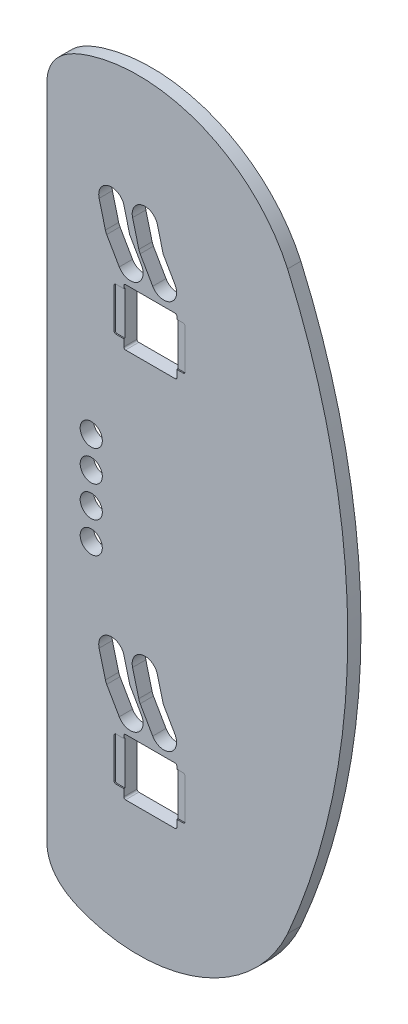
SolidWorks part; units mm, degrees
material "Pine"
ref_plane "Front Plane" through (0, 0, 0) normal (0, 0, 1) x (1, 0, 0)
ref_plane "Top Plane" through (0, 0, 0) normal (0, 1, 0) x (1, 0, 0)
ref_plane "Right Plane" through (0, 0, 0) normal (1, 0, 0) x (0, 0, -1)
sketch "Sketch1" plane through (0, 0, 0) normal (0, 1, 0) x (1, 0, 0)
  line L0 (-92.9216, 89.0184) -> (669.0784, 89.0184)
  line L1 (669.0784, 89.0184) -> (669.0784, 419.2184)
  line L2 (-92.9216, 89.0184) -> (-92.9216, 419.2184)
  line L5 (110.2784, 495.4184) -> (465.8784, 495.4184)
  line L8 (110.2784, 495.4184) -> (-92.9216, 419.2184)
  line L9 (465.8784, 495.4184) -> (669.0784, 419.2184)
  line L10 (-92.9216, 495.4184) -> (669.0784, 495.4184) construction
sketch "Sketch2" plane through (0, 0, 0) normal (0, 0, 1) x (1, 0, 0)
  line L95 (1361.0966, 1819.7347) -> (1361.0966, 996.3635)
  arc A0 (1691.2966, 1027.0491) -> (1691.2966, 1789.0491) centre (733.0004, 1408.0491) ccw
  spline S0 degree 3 poles (1691.2966, 1027.0491) (1656.7077, 922.0591) (1371.3251, 886.2968) (1361.0966, 996.3635) knots 0 0 0 0 7.629784 7.629784 7.629784 7.629784
  spline S1 degree 3 poles (1691.2966, 1789.0491) (1656.7629, 1894.0573) (1371.3251, 1929.8013) (1361.0966, 1819.7347) knots 0 0 0 0 7.638295 7.638295 7.638295 7.638295
sketch "Sketch5" plane through (0, 0, 0) normal (0, 0, 1) x (1, 0, 0)
  line L0 (1361.0966, 1819.7347) -> (1361.0966, 996.3635)
  line L1 (1361.0966, 1789.0491) -> (1361.0966, 1027.0491)
  line L2 (1540.0357, 1006.8697) -> (1540.0357, 1016.3947)
  line L3 (1486.0607, 1097.3572) -> (1486.0607, 1006.8697) construction
  line L4 (1486.0607, 1102.1197) -> (1486.0607, 1092.5947)
  line L5 (1540.0357, 1006.8697) -> (1540.0357, 1097.3572) construction
  line L6 (1544.7982, 1102.1197) -> (1481.2982, 1102.1197) construction
  line L7 (1486.0607, 1006.8697) -> (1540.0357, 1006.8697)
  line L8 (1479.7107, 1016.3947) -> (1546.3857, 1016.3947)
  line L9 (1546.3857, 1016.3947) -> (1546.3857, 1092.5947)
  line L10 (1546.3857, 1092.5947) -> (1479.7107, 1092.5947)
  line L11 (1479.7107, 1016.3947) -> (1479.7107, 1092.5947)
  line L12 (1540.0357, 1548.8399) -> (1540.0357, 1558.3649)
  line L13 (1486.0607, 1548.8399) -> (1540.0357, 1548.8399)
  line L14 (1546.3857, 1634.5649) -> (1479.7107, 1634.5649)
  line L15 (1486.0607, 1644.0899) -> (1486.0607, 1634.5649)
  line L16 (1479.7107, 1558.3649) -> (1479.7107, 1634.5649)
  line L17 (1540.0357, 1644.0899) -> (1486.0607, 1644.0899)
  line L18 (1479.7107, 1558.3649) -> (1546.3857, 1558.3649)
  line L19 (1546.3857, 1558.3649) -> (1546.3857, 1634.5649)
  line L20 (1540.0357, 1092.5947) -> (1540.0357, 1102.1197)
  line L21 (1486.0607, 1016.3947) -> (1486.0607, 1006.8697)
  line L22 (1540.0357, 1634.5649) -> (1540.0357, 1644.0899)
  line L23 (1486.0607, 1558.3649) -> (1486.0607, 1548.8399)
  line L95 (1361.0966, 1819.7347) -> (1361.0966, 996.3635)
  line L115 (1540.0357, 1102.1197) -> (1486.0607, 1102.1197)
  line L199 (1363.2449, 1823.8418) -> (1361.0966, 1819.7347)
  line L200 (1361.0966, 1819.7347) -> (1361.7967, 1824.3165)
  line L201 (1361.7967, 1824.3165) -> (1363.2449, 1823.8418)
  line L202 (1540.0357, 1097.3572) -> (1486.0607, 1097.3572) construction
  line L203 (1481.2982, 1102.1197) -> (1481.2982, 1006.8697) construction
  line L204 (1544.7982, 1006.8697) -> (1544.7982, 1102.1197) construction
  arc A0 (1691.2966, 1027.0491) -> (1691.2966, 1789.0491) centre (733.0004, 1408.0491) ccw
  circle A1 centre (1506.0488, 1194.0197) radius 15.875
  circle A2 centre (1515.0488, 1159.0198) radius 15.875
  circle A3 centre (1533.0488, 1127.7698) radius 15.875
  circle A4 centre (1467.0488, 1159.0198) radius 15.875
  circle A5 centre (1485.0488, 1127.7698) radius 15.875
  circle A6 centre (1458.0488, 1194.0197) radius 15.875
  circle A7 centre (1513.0482, 1054.4947) radius 12
  circle A8 centre (1506.0488, 1735.9899) radius 15.875
  circle A9 centre (1515.0488, 1700.99) radius 15.875
  circle A10 centre (1533.0488, 1669.74) radius 15.875
  circle A11 centre (1467.0488, 1700.99) radius 15.875
  circle A12 centre (1485.0488, 1669.74) radius 15.875
  circle A13 centre (1458.0488, 1735.9899) radius 15.875
  circle A15 centre (1483.5084, 1375.1967) radius 12
  circle A16 centre (1483.9827, 1438.6917) radius 12
  circle A17 centre (1551.8392, 1408.0266) radius 29.9999
  circle A18 centre (1409.3368, 1408.0266) radius 15.9995
  circle A19 centre (1513.0482, 1596.4649) radius 12
  arc A30 (1539.4945, 1725.9331) -> (1482.0488, 1761.3623) centre (1506.0488, 1735.9899) ccw
  arc A32 (1549.9668, 1700.2938) -> (1539.4945, 1725.9331) centre (1515.0488, 1700.99) ccw
  arc A41 (1509.0488, 1644.3676) -> (1549.9668, 1700.2938) centre (1533.0488, 1669.74) ccw
  arc A46 (1450.1308, 1670.4362) -> (1509.0488, 1644.3676) centre (1485.0488, 1669.74) ccw
  arc A47 (1433.6031, 1711.0467) -> (1450.1308, 1670.4362) centre (1467.0488, 1700.99) ccw
  arc A50 (1482.0488, 1761.3623) -> (1433.6031, 1711.0467) centre (1458.0488, 1735.9899) ccw
  arc A64 (1509.0488, 1102.3974) -> (1549.9668, 1158.3235) centre (1533.0488, 1127.7698) ccw
  arc A66 (1450.1308, 1128.466) -> (1509.0488, 1102.3974) centre (1485.0488, 1127.7698) ccw
  arc A68 (1433.6031, 1169.0765) -> (1450.1308, 1128.466) centre (1467.0488, 1159.0198) ccw
  arc A70 (1539.4945, 1183.9629) -> (1482.0488, 1219.3921) centre (1506.0488, 1194.0197) ccw
  arc A72 (1549.9668, 1158.3235) -> (1539.4945, 1183.9629) centre (1515.0488, 1159.0198) ccw
  arc A73 (1482.0488, 1219.3921) -> (1433.6031, 1169.0765) centre (1458.0488, 1194.0197) ccw
  arc A86 (1474.249, 1382.8299) -> (1489.0021, 1364.5282) centre (1483.5084, 1375.1967) ccw
  arc A89 (1488.8753, 1449.649) -> (1474.6166, 1431.19) centre (1483.9827, 1438.6917) ccw
  arc A97 (1557.861, 1378.6372) -> (1557.0728, 1437.5665) centre (1551.8392, 1408.0266) ccw
  arc A99 (1420.1657, 1419.8299) -> (1400.5179, 1421.402) centre (1409.3362, 1408.0491) ccw
  arc A100 (1402.6554, 1393.5084) -> (1419.641, 1395.8067) centre (1409.3362, 1408.0491) ccw
  spline S0 degree 3 poles (1691.2966, 1027.0491) (1656.7077, 922.0591) (1371.3251, 886.2968) (1361.0966, 996.3635) knots 0 0 0 0 7.629784 7.629784 7.629784 7.629784
  spline S1 degree 3 poles (1691.2966, 1789.0491) (1656.7629, 1894.0573) (1371.3251, 1929.8013) (1361.0966, 1819.7347) knots 0 0 0 0 7.638295 7.638295 7.638295 7.638295
  dimension "D1" = 4.7625
sketch "Sketch8" plane through (0, 0, 0) normal (0, 0, 1) x (1, 0, 0)
  line L2 (1540.0357, 1006.8697) -> (1540.0357, 1016.3947)
  line L3 (1486.0607, 1097.3572) -> (1486.0607, 1006.8697) construction
  line L4 (1486.0607, 1102.1197) -> (1486.0607, 1092.5947)
  line L5 (1540.0357, 1006.8697) -> (1540.0357, 1097.3572) construction
  line L6 (1544.7982, 1102.1197) -> (1481.2982, 1102.1197) construction
  line L7 (1486.0607, 1006.8697) -> (1540.0357, 1006.8697)
  line L8 (1479.7107, 1016.3947) -> (1546.3857, 1016.3947)
  line L9 (1546.3857, 1016.3947) -> (1546.3857, 1092.5947)
  line L10 (1546.3857, 1092.5947) -> (1479.7107, 1092.5947)
  line L11 (1479.7107, 1016.3947) -> (1479.7107, 1092.5947)
  line L12 (1540.0357, 1548.8399) -> (1540.0357, 1558.3649)
  line L13 (1486.0607, 1548.8399) -> (1540.0357, 1548.8399)
  line L14 (1546.3857, 1634.5649) -> (1479.7107, 1634.5649)
  line L15 (1486.0607, 1644.0899) -> (1486.0607, 1634.5649)
  line L16 (1479.7107, 1558.3649) -> (1479.7107, 1634.5649)
  line L17 (1540.0357, 1644.0899) -> (1486.0607, 1644.0899)
  line L18 (1479.7107, 1558.3649) -> (1546.3857, 1558.3649)
  line L19 (1546.3857, 1558.3649) -> (1546.3857, 1634.5649)
  line L20 (1540.0357, 1092.5947) -> (1540.0357, 1102.1197)
  line L21 (1486.0607, 1016.3947) -> (1486.0607, 1006.8697)
  line L22 (1540.0357, 1634.5649) -> (1540.0357, 1644.0899)
  line L23 (1486.0607, 1558.3649) -> (1486.0607, 1548.8399)
  line L95 (1361.0966, 1819.7347) -> (1361.0966, 996.3635)
  line L115 (1540.0357, 1102.1197) -> (1486.0607, 1102.1197)
  line L202 (1540.0357, 1097.3572) -> (1486.0607, 1097.3572) construction
  line L203 (1481.2982, 1102.1197) -> (1481.2982, 1006.8697) construction
  line L204 (1544.7982, 1006.8697) -> (1544.7982, 1102.1197) construction
  arc A0 (1691.2966, 1027.0491) -> (1691.2966, 1789.0491) centre (733.0004, 1408.0491) ccw
  circle A1 centre (1506.0488, 1194.0197) radius 15.875
  circle A2 centre (1515.0488, 1159.0198) radius 15.875
  circle A3 centre (1533.0488, 1127.7698) radius 15.875
  circle A4 centre (1467.0488, 1159.0198) radius 15.875
  circle A5 centre (1485.0488, 1127.7698) radius 15.875
  circle A6 centre (1458.0488, 1194.0197) radius 15.875
  circle A7 centre (1513.0482, 1054.4947) radius 12
  circle A8 centre (1506.0488, 1735.9899) radius 15.875
  circle A9 centre (1515.0488, 1700.99) radius 15.875
  circle A10 centre (1533.0488, 1669.74) radius 15.875
  circle A11 centre (1467.0488, 1700.99) radius 15.875
  circle A12 centre (1485.0488, 1669.74) radius 15.875
  circle A13 centre (1458.0488, 1735.9899) radius 15.875
  circle A15 centre (1483.5084, 1375.1967) radius 12
  circle A16 centre (1483.9827, 1438.6917) radius 12
  circle A17 centre (1551.8392, 1408.0266) radius 29.9999
  circle A18 centre (1409.3368, 1408.0266) radius 15.9995
  circle A19 centre (1513.0482, 1596.4649) radius 12
  arc A30 (1539.4945, 1725.9331) -> (1482.0488, 1761.3623) centre (1506.0488, 1735.9899) ccw
  arc A32 (1549.9668, 1700.2938) -> (1539.4945, 1725.9331) centre (1515.0488, 1700.99) ccw
  arc A41 (1509.0488, 1644.3676) -> (1549.9668, 1700.2938) centre (1533.0488, 1669.74) ccw
  arc A46 (1450.1308, 1670.4362) -> (1509.0488, 1644.3676) centre (1485.0488, 1669.74) ccw
  arc A47 (1433.6031, 1711.0467) -> (1450.1308, 1670.4362) centre (1467.0488, 1700.99) ccw
  arc A50 (1482.0488, 1761.3623) -> (1433.6031, 1711.0467) centre (1458.0488, 1735.9899) ccw
  arc A64 (1509.0488, 1102.3974) -> (1549.9668, 1158.3235) centre (1533.0488, 1127.7698) ccw
  arc A66 (1450.1308, 1128.466) -> (1509.0488, 1102.3974) centre (1485.0488, 1127.7698) ccw
  arc A68 (1433.6031, 1169.0765) -> (1450.1308, 1128.466) centre (1467.0488, 1159.0198) ccw
  arc A70 (1539.4945, 1183.9629) -> (1482.0488, 1219.3921) centre (1506.0488, 1194.0197) ccw
  arc A72 (1549.9668, 1158.3235) -> (1539.4945, 1183.9629) centre (1515.0488, 1159.0198) ccw
  arc A73 (1482.0488, 1219.3921) -> (1433.6031, 1169.0765) centre (1458.0488, 1194.0197) ccw
  arc A86 (1474.249, 1382.8299) -> (1489.0021, 1364.5282) centre (1483.5084, 1375.1967) ccw
  arc A89 (1488.8753, 1449.649) -> (1474.6166, 1431.19) centre (1483.9827, 1438.6917) ccw
  arc A97 (1557.861, 1378.6372) -> (1557.0728, 1437.5665) centre (1551.8392, 1408.0266) ccw
  arc A99 (1420.1657, 1419.8299) -> (1400.5179, 1421.402) centre (1409.3362, 1408.0491) ccw
  arc A100 (1402.6554, 1393.5084) -> (1419.641, 1395.8067) centre (1409.3362, 1408.0491) ccw
  spline S0 degree 3 poles (1691.2966, 1027.0491) (1656.7077, 922.0591) (1371.3251, 886.2968) (1361.0966, 996.3635) knots 0 0 0 0 7.629784 7.629784 7.629784 7.629784
  spline S1 degree 3 poles (1691.2966, 1789.0491) (1656.7629, 1894.0573) (1371.3251, 1929.8013) (1361.0966, 1819.7347) knots 0 0 0 0 7.638295 7.638295 7.638295 7.638295
  dimension "D1" = 4.7625
sketch "Sketch9" plane through (0, 0, 0) normal (0, 0, 1) x (1, 0, 0)
  line L0 (1361.0966, 1884.2991) -> (1361.0966, 1060.9279)
  line L1 (1361.0966, 1472.6135) -> (1839.973, 1472.6135)
  circle A20 centre (1506.0488, 1272.2885) radius 12
  circle A21 centre (1515.0488, 1237.2885) radius 12
  circle A22 centre (1533.0488, 1206.0385) radius 12
  circle A23 centre (1467.0488, 1237.2885) radius 12
  circle A24 centre (1485.0488, 1206.0385) radius 12
  circle A25 centre (1458.0488, 1272.2885) radius 12
  circle A26 centre (1513.0482, 1142.2885) radius 12
  circle A27 centre (1501.6642, 1830.4221) radius 12
  circle A28 centre (1510.6642, 1795.4221) radius 12
  circle A29 centre (1528.6642, 1764.1721) radius 12
  circle A31 centre (1462.6642, 1795.4221) radius 12
  circle A33 centre (1480.6642, 1764.1721) radius 12
  circle A34 centre (1453.6642, 1830.4221) radius 12
  circle A35 centre (1508.6636, 1700.4221) radius 12
sketch "Sketch13" plane through (0, 0, 0) normal (0, 0, 1) x (1, 0, 0)
  line L0 (1439.599, 1277.0692) -> (1448.5991, 1242.0693)
  line L1 (1450.5414, 1237.3053) -> (1468.5414, 1206.0553)
  line L2 (1540.0357, 1097.2035) -> (1540.0357, 1104.1885)
  line L3 (1486.0607, 1185.151) -> (1486.0607, 1006.8697) construction
  line L4 (1486.0607, 1187.3735) -> (1486.0607, 1180.3885)
  line L5 (1540.0357, 1006.8697) -> (1540.0357, 1185.151) construction
  line L6 (1544.7982, 1189.9135) -> (1481.2982, 1189.9135) construction
  line L7 (1488.6007, 1094.6635) -> (1537.4957, 1094.6635)
  line L8 (1482.2507, 1104.1885) -> (1543.8457, 1104.1885)
  line L9 (1546.3857, 1106.7285) -> (1546.3857, 1177.8485)
  line L10 (1543.8457, 1180.3885) -> (1482.2507, 1180.3885)
  line L11 (1479.7107, 1106.7285) -> (1479.7107, 1177.8485)
  line L12 (1540.0357, 1656.0035) -> (1540.0357, 1662.9885)
  line L13 (1488.6007, 1653.4635) -> (1537.4957, 1653.4635)
  line L14 (1543.8457, 1739.1885) -> (1482.2507, 1739.1885)
  line L15 (1486.0607, 1746.1735) -> (1486.0607, 1739.1885)
  line L16 (1479.7107, 1665.5285) -> (1479.7107, 1736.6485)
  line L17 (1537.4957, 1748.7135) -> (1488.6007, 1748.7135)
  line L18 (1482.2507, 1662.9885) -> (1543.8457, 1662.9885)
  line L19 (1546.3857, 1665.5285) -> (1546.3857, 1736.6485)
  line L20 (1540.0357, 1180.3885) -> (1540.0357, 1187.3735)
  line L21 (1486.0607, 1104.1885) -> (1486.0607, 1097.2035)
  line L22 (1540.0357, 1739.1885) -> (1540.0357, 1746.1735)
  line L23 (1486.0607, 1662.9885) -> (1486.0607, 1656.0035)
  line L24 (1485.0488, 1196.5135) -> (1533.0488, 1196.5135)
  line L25 (1550.8991, 1222.2168) -> (1533.383, 1252.007)
  line L26 (1524.4986, 1286.5577) -> (1533.383, 1252.007)
  line L27 (1459.748, 1300.7875) -> (1504.3496, 1300.7875)
  line L28 (1439.599, 1835.8692) -> (1448.5991, 1800.8693)
  line L29 (1450.5414, 1796.1053) -> (1468.5414, 1764.8553)
  line L30 (1485.0488, 1755.3135) -> (1533.0488, 1755.3135)
  line L31 (1549.5562, 1783.8718) -> (1532.852, 1812.8721)
  line L32 (1524.4986, 1845.3577) -> (1532.852, 1812.8721)
  line L33 (1458.0488, 1859.6635) -> (1506.0488, 1859.6635)
  line L34 (1513.0482, 1748.7135) -> (1513.0482, 1755.3135)
  line L38 (1513.0482, 1189.9135) -> (1513.0482, 1196.5135)
  line L95 (1361.0966, 1948.8635) -> (1361.0966, 996.3635)
  line L115 (1537.4957, 1189.9135) -> (1488.6007, 1189.9135)
  line L202 (1540.0357, 1185.151) -> (1486.0607, 1185.151) construction
  line L203 (1481.2982, 1189.9135) -> (1481.2982, 1006.8697) construction
  line L204 (1544.7982, 1006.8697) -> (1544.7982, 1189.9135) construction
  arc A0 (1691.2966, 1027.0491) -> (1691.2966, 1918.1779) centre (761.2616, 1472.6135) ccw
  arc A1 (1524.4986, 1286.5577) -> (1504.3496, 1300.7875) centre (1506.0488, 1281.8135) ccw
  arc A2 (1479.7107, 1177.8485) -> (1482.2507, 1180.3885) centre (1482.2507, 1177.8485) cw
  arc A3 (1533.0488, 1196.5135) -> (1547.5414, 1227.9274) centre (1533.0488, 1215.5635) ccw
  arc A4 (1448.5991, 1242.0693) -> (1450.5414, 1237.3053) centre (1467.0488, 1246.8135) ccw
  arc A5 (1468.5414, 1206.0553) -> (1485.0488, 1196.5135) centre (1485.0488, 1215.5635) ccw
  arc A6 (1459.748, 1300.7875) -> (1439.599, 1277.0692) centre (1458.0488, 1281.8135) ccw
  circle A7 centre (1513.0482, 1142.2885) radius 12
  arc A8 (1524.4986, 1845.3577) -> (1506.0488, 1859.6635) centre (1506.0488, 1840.6135) ccw
  arc A9 (1546.3857, 1177.8485) -> (1543.8457, 1180.3885) centre (1543.8457, 1177.8485) ccw
  arc A10 (1533.0488, 1755.3135) -> (1549.5562, 1783.8718) centre (1533.0488, 1774.3635) ccw
  arc A11 (1448.5991, 1800.8693) -> (1450.5414, 1796.1053) centre (1467.0488, 1805.6135) ccw
  arc A12 (1543.8457, 1104.1885) -> (1546.3857, 1106.7285) centre (1543.8457, 1106.7285) ccw
  arc A13 (1458.0488, 1859.6635) -> (1439.599, 1835.8692) centre (1458.0488, 1840.6135) ccw
  arc A14 (1482.2507, 1104.1885) -> (1479.7107, 1106.7285) centre (1482.2507, 1106.7285) cw
  arc A15 (1488.6007, 1094.6635) -> (1486.0607, 1097.2035) centre (1488.6007, 1097.2035) cw
  arc A16 (1537.4957, 1094.6635) -> (1540.0357, 1097.2035) centre (1537.4957, 1097.2035) ccw
  arc A17 (1479.7107, 1736.6485) -> (1482.2507, 1739.1885) centre (1482.2507, 1736.6485) cw
  arc A18 (1546.3857, 1736.6485) -> (1543.8457, 1739.1885) centre (1543.8457, 1736.6485) ccw
  circle A19 centre (1513.0482, 1701.0885) radius 12
  arc A20 (1468.5414, 1764.8553) -> (1485.0488, 1755.3135) centre (1485.0488, 1774.3635) ccw
  arc A21 (1540.0357, 1746.1735) -> (1537.4957, 1748.7135) centre (1537.4957, 1746.1735) ccw
  arc A22 (1486.0607, 1746.1735) -> (1488.6007, 1748.7135) centre (1488.6007, 1746.1735) cw
  arc A23 (1543.8457, 1662.9885) -> (1546.3857, 1665.5285) centre (1543.8457, 1665.5285) ccw
  arc A24 (1537.4957, 1653.4635) -> (1540.0357, 1656.0035) centre (1537.4957, 1656.0035) ccw
  arc A25 (1488.6007, 1653.4635) -> (1486.0607, 1656.0035) centre (1488.6007, 1656.0035) cw
  arc A26 (1479.7107, 1665.5285) -> (1482.2507, 1662.9885) centre (1482.2507, 1665.5285) ccw
  arc A27 (1540.0357, 1187.3735) -> (1537.4957, 1189.9135) centre (1537.4957, 1187.3735) ccw
  arc A28 (1486.0607, 1187.3735) -> (1488.6007, 1189.9135) centre (1488.6007, 1187.3735) cw
  circle A29 centre (1424.5966, 1539.2885) radius 15.875
  circle A30 centre (1424.5966, 1494.8385) radius 15.875
  circle A31 centre (1424.5966, 1450.3885) radius 15.875
  circle A32 centre (1424.5966, 1405.9385) radius 15.875
  spline S0 degree 3 poles (1691.2966, 1027.0491) (1656.7077, 922.0591) (1371.3251, 886.2968) (1361.0966, 996.3635) knots 0 0 0 0 7.629784 7.629784 7.629784 7.629784
  spline S1 degree 3 poles (1691.2966, 1918.1779) (1656.7629, 2023.1861) (1371.3251, 2058.9302) (1361.0966, 1948.8635) knots 0 0 0 0 7.638295 7.638295 7.638295 7.638295
  dimension "D2" = 2.54
  dimension "D4" = 2.54
  dimension "D5" = 2.54
  dimension "D6" = 2.54
  dimension "D7" = 2.54
  dimension "D8" = 2.54
  dimension "D9" = 2.54
  dimension "D3" = 2.54
  dimension "D15" = 2.54
  dimension "D1" = 4.7625
sketch "Sketch17" plane through (0, 0, 0) normal (0, 0, 1) x (1, 0, 0)
  line L2 (1509.3308, 1749.8224) -> (1509.3308, 1754.2046)
  line L4 (1523.1267, 1289.3333) -> (1531.2884, 1257.5934)
  line L5 (1459.9849, 1122.4424) -> (1556.5049, 1122.4424)
  line L6 (1531.5474, 1256.9582) -> (1547.8672, 1228.6251)
  line L7 (1547.4308, 1184.6724) -> (1556.5049, 1184.6724)
  line L8 (1432.2032, 1278.2957) -> (1441.2032, 1243.2958)
  line L9 (1547.4308, 1112.2824) -> (1547.4308, 1188.4824)
  line L10 (1459.9849, 1184.6724) -> (1471.2308, 1184.6724)
  line L11 (1473.7708, 1191.0224) -> (1544.8908, 1191.0224)
  line L14 (1547.4308, 1671.0824) -> (1547.4308, 1747.2824)
  line L15 (1471.2308, 1188.4824) -> (1471.2308, 1112.2824)
  line L16 (1473.7708, 1749.8224) -> (1544.8908, 1749.8224)
  line L17 (1432.2032, 1837.0957) -> (1441.2032, 1802.0958)
  line L18 (1471.2308, 1747.2824) -> (1471.2308, 1671.0824)
  line L19 (1461.4626, 1765.304) -> (1443.4626, 1796.554)
  line L20 (1461.4626, 1206.504) -> (1443.4626, 1237.754)
  line L21 (1547.4308, 1122.4424) -> (1556.5049, 1122.4424)
  line L22 (1547.4308, 1681.2424) -> (1556.5049, 1681.2424)
  line L23 (1523.1267, 1848.1333) -> (1531.2884, 1816.3934)
  line L24 (1453.665, 1305.9745) -> (1501.6649, 1305.9745)
  line L26 (1473.7708, 1109.7424) -> (1544.8908, 1109.7424)
  line L27 (1480.665, 1754.2046) -> (1528.6649, 1754.2046)
  line L28 (1531.5474, 1815.7582) -> (1547.8672, 1787.4251)
  line L29 (1453.665, 1864.7745) -> (1501.6649, 1864.7745)
  line L30 (1480.665, 1195.4046) -> (1528.6649, 1195.4046)
  line L31 (1559.0449, 1182.1324) -> (1559.0449, 1124.9824)
  line L32 (1457.4449, 1182.1324) -> (1457.4449, 1124.9824)
  line L34 (1457.4449, 1740.9324) -> (1457.4449, 1683.7824)
  line L35 (1473.7708, 1668.5424) -> (1544.8908, 1668.5424)
  line L36 (1459.9849, 1743.4724) -> (1471.2308, 1743.4724)
  line L37 (1559.0449, 1740.9324) -> (1559.0449, 1683.7824)
  line L39 (1459.9849, 1681.2424) -> (1556.5049, 1681.2424)
  line L41 (1547.4308, 1743.4724) -> (1556.5049, 1743.4724)
  line L95 (1361.0966, 1948.8635) -> (1361.0966, 996.3635)
  arc A0 (1691.2966, 1027.0491) -> (1691.2966, 1918.1779) centre (761.2616, 1472.6135) ccw
  arc A1 (1441.2032, 1802.0958) -> (1443.4626, 1796.554) centre (1462.665, 1807.6146) ccw
  arc A2 (1523.1267, 1289.3333) -> (1501.6649, 1305.9745) centre (1501.6649, 1283.8145) ccw
  circle A3 centre (1510.6649, 1248.8146) radius 12
  arc A4 (1471.2308, 1188.4824) -> (1473.7708, 1191.0224) centre (1473.7708, 1188.4824) cw
  arc A5 (1531.5474, 1256.9582) -> (1531.2884, 1257.5934) centre (1533.7484, 1258.226) cw
  arc A6 (1461.4626, 1765.304) -> (1480.665, 1754.2046) centre (1480.665, 1776.3646) ccw
  circle A7 centre (1462.665, 1248.8146) radius 12
  arc A8 (1453.665, 1864.7745) -> (1432.2032, 1837.0957) centre (1453.665, 1842.6145) ccw
  circle A9 centre (1508.6644, 1153.8145) radius 12
  arc A10 (1523.1267, 1848.1333) -> (1501.6649, 1864.7745) centre (1501.6649, 1842.6145) ccw
  arc A11 (1531.5474, 1815.7582) -> (1531.2884, 1816.3934) centre (1533.7484, 1817.026) cw
  arc A12 (1441.2032, 1243.2958) -> (1443.4626, 1237.754) centre (1462.665, 1248.8146) ccw
  arc A13 (1528.6649, 1754.2046) -> (1547.8672, 1787.4251) centre (1528.6649, 1776.3646) ccw
  arc A14 (1528.6649, 1195.4046) -> (1547.8672, 1228.6251) centre (1528.6649, 1217.5646) ccw
  arc A15 (1544.8908, 1191.0224) -> (1547.4308, 1188.4824) centre (1544.8908, 1188.4824) cw
  arc A16 (1453.665, 1305.9745) -> (1432.2032, 1278.2957) centre (1453.665, 1283.8145) ccw
  arc A17 (1471.2308, 1747.2824) -> (1473.7708, 1749.8224) centre (1473.7708, 1747.2824) cw
  arc A18 (1473.7708, 1668.5424) -> (1471.2308, 1671.0824) centre (1473.7708, 1671.0824) cw
  circle A19 centre (1508.6644, 1712.6145) radius 12
  circle A20 centre (1453.665, 1283.8145) radius 12
  circle A21 centre (1528.6649, 1217.5646) radius 12
  arc A22 (1556.5049, 1122.4424) -> (1559.0449, 1124.9824) centre (1556.5049, 1124.9824) ccw
  arc A23 (1544.8908, 1668.5424) -> (1547.4308, 1671.0824) centre (1544.8908, 1671.0824) ccw
  circle A24 centre (1480.665, 1217.5646) radius 12
  arc A25 (1556.5049, 1184.6724) -> (1559.0449, 1182.1324) centre (1556.5049, 1182.1324) cw
  arc A26 (1544.8908, 1749.8224) -> (1547.4308, 1747.2824) centre (1544.8908, 1747.2824) cw
  arc A27 (1473.7708, 1109.7424) -> (1471.2308, 1112.2824) centre (1473.7708, 1112.2824) cw
  circle A28 centre (1501.6649, 1283.8145) radius 12
  circle A29 centre (1424.5966, 1539.2885) radius 15.875
  circle A30 centre (1424.5966, 1494.8385) radius 15.875
  circle A31 centre (1424.5966, 1450.3885) radius 15.875
  circle A32 centre (1424.5966, 1405.9385) radius 15.875
  arc A33 (1459.9849, 1743.4724) -> (1457.4449, 1740.9324) centre (1459.9849, 1740.9324) ccw
  arc A34 (1457.4449, 1683.7824) -> (1459.9849, 1681.2424) centre (1459.9849, 1683.7824) ccw
  arc A35 (1556.5049, 1681.2424) -> (1559.0449, 1683.7824) centre (1556.5049, 1683.7824) ccw
  arc A36 (1556.5049, 1743.4724) -> (1559.0449, 1740.9324) centre (1556.5049, 1740.9324) cw
  arc A37 (1459.9849, 1184.6724) -> (1457.4449, 1182.1324) centre (1459.9849, 1182.1324) ccw
  arc A38 (1461.4626, 1206.504) -> (1480.665, 1195.4046) centre (1480.665, 1217.5646) ccw
  arc A39 (1544.8908, 1109.7424) -> (1547.4308, 1112.2824) centre (1544.8908, 1112.2824) ccw
  circle A40 centre (1501.6649, 1842.6145) radius 12
  circle A41 centre (1510.6649, 1807.6146) radius 12
  circle A42 centre (1528.6649, 1776.3646) radius 12
  circle A43 centre (1462.665, 1807.6146) radius 12
  circle A44 centre (1480.665, 1776.3646) radius 12
  circle A45 centre (1453.665, 1842.6145) radius 12
  circle A46 centre (1508.6644, 1712.6145) radius 12
  arc A47 (1457.4449, 1124.9824) -> (1459.9849, 1122.4424) centre (1459.9849, 1124.9824) ccw
  spline S0 degree 3 poles (1691.2966, 1027.0491) (1656.7077, 922.0591) (1371.3251, 886.2968) (1361.0966, 996.3635) knots 0 0 0 0 7.629784 7.629784 7.629784 7.629784
  spline S1 degree 3 poles (1691.2966, 1918.1779) (1656.7629, 2023.1861) (1371.3251, 2058.9302) (1361.0966, 1948.8635) knots 0 0 0 0 7.638295 7.638295 7.638295 7.638295
  dimension "D3" = 2.54
  dimension "D10" = 2.54
sketch "Sketch19" plane through (0, 0, 0) normal (0, 0, 1) x (1, 0, 0)
  line L0 (1435.8931, 1279.2446) -> (1444.8931, 1244.2446)
  line L1 (1446.7641, 1239.6556) -> (1464.7641, 1208.4056)
  line L2 (1435.8931, 1838.0446) -> (1444.8931, 1803.0447)
  line L3 (1446.7641, 1798.4557) -> (1464.7641, 1767.2057)
  line L4 (1544.5658, 1226.7235) -> (1527.9867, 1255.5065)
  line L5 (1459.9849, 1122.4424) -> (1556.5049, 1122.4424)
  line L6 (1519.4367, 1288.3844) -> (1527.7277, 1256.1417)
  line L7 (1547.4308, 1184.6724) -> (1556.5049, 1184.6724)
  line L8 (1483.8946, 1279.2387) -> (1493.0723, 1243.5972)
  line L9 (1547.4308, 1112.2824) -> (1547.4308, 1188.4824)
  line L10 (1459.9849, 1184.6724) -> (1471.2308, 1184.6724)
  line L11 (1473.7708, 1191.0224) -> (1544.8908, 1191.0224)
  line L12 (1494.764, 1239.6557) -> (1512.764, 1208.4057)
  line L13 (1471.4367, 1288.3844) -> (1479.7345, 1256.1153)
  line L14 (1547.4308, 1671.0824) -> (1547.4308, 1747.2824)
  line L15 (1471.2308, 1188.4824) -> (1471.2308, 1112.2824)
  line L16 (1473.7708, 1749.8224) -> (1544.8908, 1749.8224)
  line L17 (1479.9868, 1814.3065) -> (1496.5658, 1785.5234)
  line L18 (1471.2308, 1747.2824) -> (1471.2308, 1671.0824)
  line L19 (1471.4368, 1847.1844) -> (1479.7278, 1814.9417)
  line L20 (1497.4224, 1225.0419) -> (1479.9903, 1255.4858)
  line L21 (1547.4308, 1122.4424) -> (1556.5049, 1122.4424)
  line L22 (1547.4308, 1681.2424) -> (1556.5049, 1681.2424)
  line L23 (1483.8931, 1838.0446) -> (1492.8931, 1803.0447)
  line L24 (1494.764, 1798.4557) -> (1512.764, 1767.2057)
  line L25 (1527.9867, 1814.3065) -> (1544.5658, 1785.5235)
  line L26 (1473.7708, 1109.7424) -> (1544.8908, 1109.7424)
  line L27 (1527.7277, 1814.9417) -> (1519.4367, 1847.1844)
  line L31 (1559.0449, 1182.1324) -> (1559.0449, 1124.9824)
  line L32 (1457.4449, 1182.1324) -> (1457.4449, 1124.9824)
  line L34 (1457.4449, 1740.9324) -> (1457.4449, 1683.7824)
  line L35 (1473.7708, 1668.5424) -> (1544.8908, 1668.5424)
  line L36 (1459.9849, 1743.4724) -> (1471.2308, 1743.4724)
  line L37 (1559.0449, 1740.9324) -> (1559.0449, 1683.7824)
  line L39 (1459.9849, 1681.2424) -> (1556.5049, 1681.2424)
  line L41 (1547.4308, 1743.4724) -> (1556.5049, 1743.4724)
  line L95 (1361.0966, 1948.8635) -> (1361.0966, 996.3635)
  arc A0 (1706.2361, 1059.6777) -> (1706.2361, 1885.5492) centre (761.2616, 1472.6135) ccw
  arc A1 (1471.4368, 1847.1844) -> (1435.8931, 1838.0446) centre (1453.665, 1842.6145) ccw
  arc A2 (1471.4367, 1288.3844) -> (1435.8931, 1279.2446) centre (1453.6649, 1283.8145) ccw
  circle A3 centre (1510.6649, 1248.8146) radius 12
  arc A4 (1471.2308, 1188.4824) -> (1473.7708, 1191.0224) centre (1473.7708, 1188.4824) cw
  arc A5 (1444.8931, 1244.2446) -> (1446.7641, 1239.6556) centre (1462.6649, 1248.8145) ccw
  arc A6 (1479.9868, 1814.3065) -> (1479.7278, 1814.9417) centre (1482.1878, 1815.5743) cw
  circle A7 centre (1462.6649, 1248.8145) radius 12
  arc A8 (1464.7641, 1767.2057) -> (1496.5658, 1785.5234) centre (1480.6649, 1776.3646) ccw
  circle A9 centre (1508.6644, 1153.8145) radius 12
  arc A10 (1492.8931, 1803.0447) -> (1494.764, 1798.4557) centre (1510.6649, 1807.6146) ccw
  arc A12 (1464.7641, 1208.4056) -> (1495.5958, 1228.2319) centre (1480.665, 1217.5646) ccw
  arc A13 (1519.4367, 1847.1844) -> (1483.8931, 1838.0446) centre (1501.6649, 1842.6145) ccw
  arc A14 (1512.764, 1208.4057) -> (1544.5658, 1226.7235) centre (1528.6649, 1217.5646) ccw
  arc A15 (1544.8908, 1191.0224) -> (1547.4308, 1188.4824) centre (1544.8908, 1188.4824) cw
  arc A16 (1527.9867, 1255.5065) -> (1527.7277, 1256.1417) centre (1530.1877, 1256.7743) cw
  arc A17 (1471.2308, 1747.2824) -> (1473.7708, 1749.8224) centre (1473.7708, 1747.2824) cw
  arc A18 (1473.7708, 1668.5424) -> (1471.2308, 1671.0824) centre (1473.7708, 1671.0824) cw
  circle A19 centre (1508.6644, 1712.6145) radius 12
  circle A20 centre (1453.6649, 1283.8145) radius 12
  circle A21 centre (1528.6649, 1217.5646) radius 12
  arc A22 (1556.5049, 1122.4424) -> (1559.0449, 1124.9824) centre (1556.5049, 1124.9824) ccw
  arc A23 (1544.8908, 1668.5424) -> (1547.4308, 1671.0824) centre (1544.8908, 1671.0824) ccw
  circle A24 centre (1480.665, 1217.5646) radius 12
  arc A25 (1556.5049, 1184.6724) -> (1559.0449, 1182.1324) centre (1556.5049, 1182.1324) cw
  arc A26 (1544.8908, 1749.8224) -> (1547.4308, 1747.2824) centre (1544.8908, 1747.2824) cw
  arc A27 (1473.7708, 1109.7424) -> (1471.2308, 1112.2824) centre (1473.7708, 1112.2824) cw
  circle A28 centre (1501.6649, 1283.8145) radius 12
  circle A29 centre (1424.5966, 1539.2885) radius 15.875
  circle A30 centre (1424.5966, 1494.8385) radius 15.875
  circle A31 centre (1424.5966, 1450.3885) radius 15.875
  circle A32 centre (1424.5966, 1405.9385) radius 15.875
  arc A33 (1459.9849, 1743.4724) -> (1457.4449, 1740.9324) centre (1459.9849, 1740.9324) ccw
  arc A34 (1457.4449, 1683.7824) -> (1459.9849, 1681.2424) centre (1459.9849, 1683.7824) ccw
  arc A35 (1556.5049, 1681.2424) -> (1559.0449, 1683.7824) centre (1556.5049, 1683.7824) ccw
  arc A36 (1556.5049, 1743.4724) -> (1559.0449, 1740.9324) centre (1556.5049, 1740.9324) cw
  arc A37 (1459.9849, 1184.6724) -> (1457.4449, 1182.1324) centre (1459.9849, 1182.1324) ccw
  arc A38 (1519.4367, 1288.3844) -> (1483.8946, 1279.2387) centre (1501.6649, 1283.8145) ccw
  arc A39 (1544.8908, 1109.7424) -> (1547.4308, 1112.2824) centre (1544.8908, 1112.2824) ccw
  circle A40 centre (1501.6649, 1842.6145) radius 12
  circle A41 centre (1510.6649, 1807.6146) radius 12
  circle A42 centre (1528.6649, 1776.3646) radius 12
  circle A43 centre (1462.665, 1807.6146) radius 12
  circle A44 centre (1480.6649, 1776.3646) radius 12
  circle A45 centre (1453.665, 1842.6145) radius 12
  circle A46 centre (1508.6644, 1712.6145) radius 12
  arc A47 (1457.4449, 1124.9824) -> (1459.9849, 1122.4424) centre (1459.9849, 1124.9824) ccw
  circle A48 centre (1462.6649, 1248.8145) radius 18.35 construction
  circle A49 centre (1453.6649, 1283.8145) radius 18.35 construction
  circle A50 centre (1480.665, 1217.5646) radius 18.35 construction
  arc A51 (1479.9903, 1255.4858) -> (1479.7345, 1256.1153) centre (1482.1945, 1256.7479) cw
  circle A52 centre (1528.6649, 1217.5646) radius 18.35 construction
  arc A53 (1512.764, 1767.2057) -> (1544.5658, 1785.5235) centre (1528.6649, 1776.3646) ccw
  circle A54 centre (1501.6649, 1842.6145) radius 18.35 construction
  circle A55 centre (1501.6649, 1283.8145) radius 18.35 construction
  circle A56 centre (1510.6649, 1807.6146) radius 18.35 construction
  arc A57 (1492.7403, 1244.8863) -> (1494.764, 1239.6557) centre (1510.6649, 1248.8146) ccw
  arc A58 (1527.9867, 1814.3065) -> (1527.7277, 1814.9417) centre (1530.1877, 1815.5743) cw
  circle A59 centre (1528.6649, 1776.3646) radius 18.35 construction
  circle A60 centre (1480.6649, 1776.3646) radius 18.35 construction
  arc A61 (1444.8931, 1803.0447) -> (1446.7641, 1798.4557) centre (1462.665, 1807.6146) ccw
  circle A62 centre (1453.665, 1842.6145) radius 18.35 construction
  spline S1 degree 3 poles (1361.0966, 996.3635) (1364.4008, 961.2038) (1498.6132, 888.7647) (1658.3076, 954.5721) (1706.2361, 1059.6777) knots 0 0 0 0 0.219674 1 1 1 1
  spline S2 degree 3 poles (1361.0966, 1948.8635) (1364.4008, 1984.0232) (1498.6132, 2056.4623) (1658.3076, 1990.6549) (1706.2361, 1885.5492) knots 0 0 0 0 0.219674 1 1 1 1
  dimension "D3" = 2.54
  dimension "D10" = 2.54
extrude "Boss-Extrude2" add sketch "Sketch19" along normal blind 19.05 contours A0 L95 L41 A36 L37 A35 L22 L14 A23 L35 A18 L18 L39 A34 L34 A33 L36 A17 L16 A26 A29 A30 A31 A32 A47 L32 A37 L10 L15 A4 L11 A15 L9 L7 A25 L31 A22 L5 A39 L26 region at (1560.3316, 1472.1078, 0)
extrude "Boss-Extrude3" add sketch "Sketch17" along normal blind 17.4625 contours L34 A34 L39 L18 L36 A33 | A36 L41 L14 L22 A35 L37 | A25 L7 L9 L5 A22 L31 | L32 A47 L5 L15 L10 A37 region at (1464.3583, 1712.3574, 0) region at (1553.2177, 1712.3574, 0) region at (1553.2177, 1153.5574, 0) region at (1464.3583, 1153.5574, 0)
